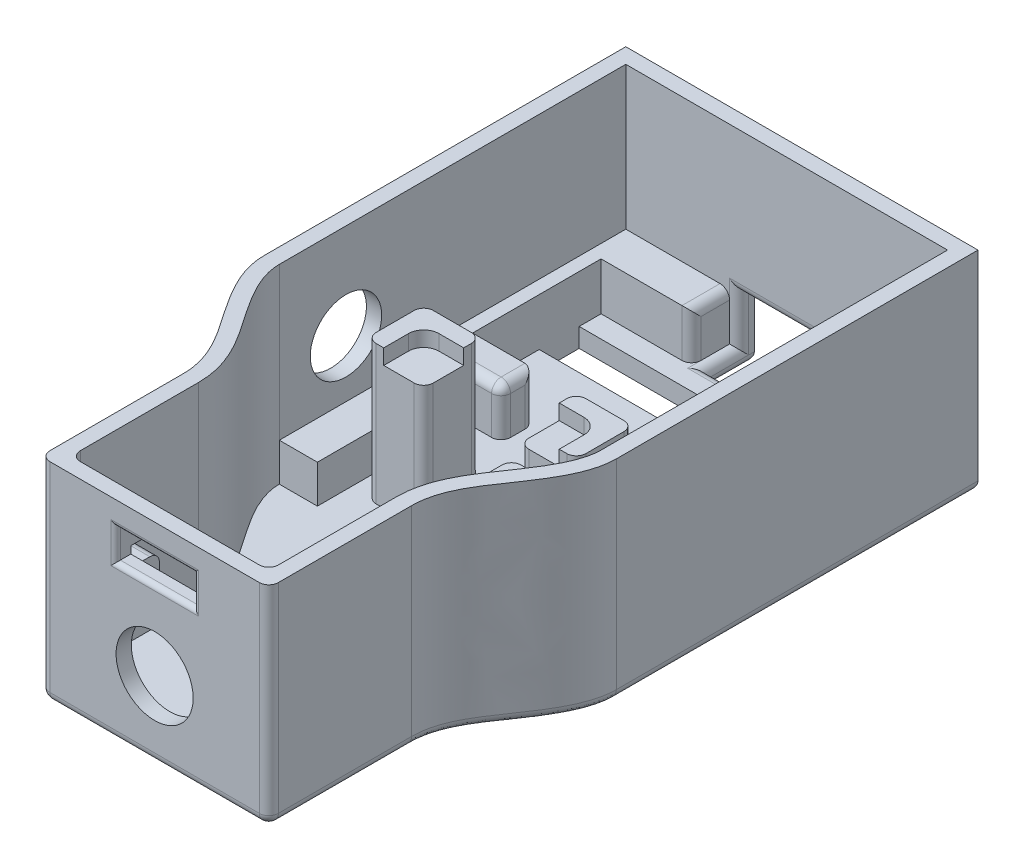
SolidWorks part; units mm, degrees
material "Melamine resin"
ref_plane "Front Plane" through (0, 0, 0) normal (0, 0, 1) x (1, 0, 0)
ref_plane "Top Plane" through (0, 0, 0) normal (0, 1, 0) x (1, 0, 0)
ref_plane "Right Plane" through (0, 0, 0) normal (1, 0, 0) x (0, 0, -1)
sketch "Sketch1" plane through (0, 0, 0) normal (0, 1, 0) x (1, 0, 0)
  line L0 (-18.5, 68) -> (0, 68)
  line L9 (0, 68) -> (0, 0)
  line L10 (-18.5, 68) -> (-18.5, 30)
  line L11 (0, 0) -> (-12, 0)
  line L12 (-12, 0) -> (-12, 15)
  line L13 (-18.5, 30) -> (-12, 30) construction
  line L14 (-12, 30) -> (-12, 15) construction
  line L15 (-15.25, 22.5) -> (-12, 22.5) construction
  line L16 (0, 1.6) -> (-10.4, 1.6)
  line L17 (-15.25, 30) -> (-15.25, 22.5) construction
  line L18 (-10.4, 1.6) -> (-10.4, 15)
  line L19 (-16.9, 66.4) -> (-16.9, 30)
  line L20 (-16.9, 66.4) -> (0, 66.4)
  line L21 (0, 68) -> (0, 66.4)
  line L22 (0, 1.6) -> (0, 0)
  spline S0 degree 3 poles (-18.5, 30) (-18.5, 27.3947) (-15.25, 22.3602) (-12, 17.8849) (-12, 15) knots 0 0 0 0 0.5 1 1 1 1
  spline S1 degree 1 poles (-16.9, 30) (-10.4, 15) knots 0 0 1 1 construction
  spline S2 degree 3 poles (-10.4, 15) (-10.4, 15.4256) (-10.4616, 16.2904) (-10.7983, 17.8861) (-11.54, 19.6983) (-12.6996, 21.6224) (-13.9392, 23.4086) (-15.1181, 25.1604) (-16.1016, 26.879) (-16.6415, 28.2398) (-16.8623, 29.268) (-16.9, 29.7529) (-16.9, 30) knots 0 0 0 0 0.0625 0.125 0.25 0.375 0.5 0.625 0.75 0.875 0.9375 1 1 1 1
  dimension "D1" = 18.5
  dimension "D2" = 68
  dimension "D3" = 15
  dimension "D4" = 15
  dimension "D5" = 12
  dimension "D6" = 1.6
extrude "Boss-Extrude1" add sketch "Sketch1" against normal blind 2 contours S0 L12 L11 L9 L0 L10
extrude "Boss-Extrude2" add sketch "Sketch1<3>" along normal blind 20 contours L18 S2 L19 L20 L9 L0 L10 S0 L12 L11 L16 region at (-9.25, 0, -67.2953)
sketch "Sketch1<3>" plane through (0, 0, 0) normal (0, 1, 0) x (1, 0, 0) same geometry as "Sketch1"
fillet "Fillet1" radius 1 2 edges at (-10.4, 10, -1.6) (-12, 9, 0)
mirror "Mirror1" about plane through (0, 0, 0) normal (1, 0, 0) of "Boss-Extrude2", "Fillet1", "Boss-Extrude1"
sketch "Sketch2" plane through (0, 0, 0) normal (0, 0, 1) x (1, 0, 0)
  line L0 (0, 0) -> (0, 6) construction
  line L1 (0, 6) -> (0, 15.84) construction
  line L2 (4.1, 14.24) -> (-4.1, 14.24)
  line L3 (4.1, 14.24) -> (4.1, 17.44)
  line L4 (4.1, 17.44) -> (-4.1, 17.44)
  line L5 (-4.1, 14.24) -> (-4.1, 17.44)
  line L6 (4.1, 14.24) -> (-4.1, 17.44) construction
  line L7 (4.1, 17.44) -> (-4.1, 14.24) construction
  line L8 (11, 20) -> (-11, 20) construction
  circle A0 centre (0, 6) radius 4.05
  point P4 (0, 15.84)
  dimension "D1" = 8.1
  dimension "D2" = 6
  dimension "D3" = 8.2
  dimension "D4" = 3.2
  dimension "D5" = 4.16
extrude "Cut-Extrude1" cut sketch "Sketch2" against normal up to next
sketch "Sketch3" plane through (0, 0, 0) normal (0, 1, 0) x (1, 0, 0)
  line L0 (-15.5, 55.65) -> (15.5, 55.65) construction
  line L1 (-16.9, 66.4) -> (-6, 66.4)
  line L2 (-16.9, 66.4) -> (-16.9, 45.4)
  line L3 (-16.9, 45.4) -> (-9, 45.4)
  line L4 (16.9, 66.4) -> (16.9, 45.4)
  line L5 (9, 45.4) -> (16.9, 45.4)
  line L7 (-9, 48.9) -> (-9, 45.4)
  line L9 (9, 48.9) -> (9, 45.4)
  line L10 (9, 48.9) -> (15.5, 48.9)
  line L11 (-15.5, 62.4) -> (-6, 62.4)
  line L12 (-15.5, 62.4) -> (-15.5, 48.9)
  line L13 (-15.5, 48.9) -> (-9, 48.9)
  line L14 (15.5, 62.4) -> (15.5, 48.9)
  line L15 (-9, 45.4) -> (9, 45.4) construction
  line L16 (-9, 48.9) -> (9, 48.9) construction
  line L17 (0, 66.4) -> (0, 62.4) construction
  line L18 (0, 62.4) -> (0, 48.9) construction
  line L19 (0, 48.9) -> (0, 45.4) construction
  line L20 (16.9, 66.4) -> (16.9, 30) construction
  line L21 (-6, 62.4) -> (-6, 66.4)
  line L22 (6, 62.4) -> (6, 66.4)
  line L23 (6, 62.4) -> (15.5, 62.4)
  line L24 (6, 66.4) -> (16.9, 66.4)
  line L25 (-6, 66.4) -> (6, 66.4) construction
  line L26 (-16.9, 66.4) -> (16.9, 66.4) construction
  line L27 (-6, 62.4) -> (6, 62.4) construction
  point P23 (0, 55.65)
  dimension "D1" = 31
  dimension "D2" = 13.5
  dimension "D3" = 12
  dimension "D4" = 4
  dimension "D5" = 18
  dimension "D6" = 3.5
extrude "Boss-Extrude3" add sketch "Sketch3" along normal blind 5
ref_plane "IR_mid" through (0, 0, -55.65) normal (0, 0, 1) x (1, 0, 0)
sketch "Sketch4" plane through (0, 0, -68) normal (0, 0, -1) x (-1, 0, 0)
  line L0 (18.5, -2) -> (-18.5, -2) construction
  line L1 (-5, -2) -> (5, -2)
  line L2 (-5, -2) -> (-5, 5)
  line L3 (-5, 5) -> (5, 5)
  line L4 (5, -2) -> (5, 5)
  line L5 (0, 5) -> (0, -2) construction
  dimension "D1" = 10
  dimension "D2" = 7
extrude "Cut-Extrude2" cut sketch "Sketch4" against normal blind 5
sketch "Sketch5" plane through (-18.5, 0, 0) normal (-1, 0, 0) x (0, 0, 1)
  line L0 (-37, 20) -> (-37, 0) construction
  line L1 (-68, 20) -> (-30, 20) construction
  line L2 (-37, 0) -> (0, 0) construction
  circle A0 centre (-37, 10) radius 3.75
  dimension "D1" = 7.5
  dimension "D2" = 37
extrude "Cut-Extrude3" cut sketch "Sketch5" against normal up to next
sketch "Sketch6" plane through (0, 0, 0) normal (0, 1, 0) x (1, 0, 0)
  line L0 (-16.9, 45.4) -> (-16.9, 30) construction
  line L1 (-16.9, 45.4) -> (-12.9, 45.4)
  line L2 (-16.9, 45.4) -> (-16.9, 30)
  line L3 (-16.9, 30) -> (-12.9, 30)
  line L4 (-12.9, 45.4) -> (-12.9, 30)
  spline S0 degree 3 poles (-10.4, 15) (-10.4, 15.4256) (-10.4616, 16.2904) (-10.7983, 17.8861) (-11.54, 19.6983) (-12.6996, 21.6224) (-13.9392, 23.4086) (-15.1181, 25.1604) (-16.1016, 26.879) (-16.6415, 28.2398) (-16.8623, 29.268) (-16.9, 29.7529) (-16.9, 30) knots 0 0 0 0 0.0625 0.125 0.25 0.375 0.5 0.625 0.75 0.875 0.9375 1 1 1 1 construction
  dimension "D1" = 4
extrude "Boss-Extrude4" add sketch "Sketch6" along normal blind 4
sketch "Sketch7" plane through (0, 0, -1.6) normal (0, 0, -1) x (-1, 0, 0)
  line L0 (4.1, 13) -> (9, 13)
  line L1 (11.1, 11) -> (4.1, 11)
  line L4 (4.1, 11) -> (4.1, 13)
  line L5 (9, 13) -> (9, 15)
  line L10 (4.1, 11) -> (0, 11) construction
  line L11 (9, 15) -> (4.1, 15)
  line L12 (-9.4, 0) -> (9.4, 0) construction
  line L13 (0, 0) -> (0, 11) construction
  line L14 (4.1, 15) -> (4.1, 17)
  line L15 (4.1, 17) -> (11.1, 17)
  line L16 (11.1, 11) -> (11.1, 17)
  line L17 (4.1, 13) -> (4.1, 15) construction
  dimension "D1" = 7
  dimension "D2" = 2
  dimension "D3" = 11
  dimension "D4" = 4.1
  dimension "D5" = 2
  dimension "D6" = 9
extrude "Boss-Extrude5" add sketch "Sketch7" along normal blind 3
sketch "Sketch9" plane through (0, 0, 0) normal (0, 1, 0) x (1, 0, 0)
  line L0 (0, 0) -> (0, 36.788) construction
  line L1 (-5.018, 33.288) -> (-11.018, 33.288)
  line L2 (-5.018, 33.288) -> (-5.018, 39.288)
  line L3 (-5.018, 39.288) -> (-11.018, 39.288)
  line L4 (-11.018, 33.288) -> (-11.018, 39.288)
  line L5 (-8.518, 36.788) -> (-8.518, 39.288) construction
  line L6 (-8.518, 36.788) -> (-11.018, 36.788) construction
  line L7 (0, 36.788) -> (-8.518, 36.788) construction
  point P0 (-8.518, 36.788)
  dimension "D1" = 2.5
  dimension "D2" = 2.5
  dimension "D3" = 8.518
  dimension "D4" = 36.788
  dimension "D5" = 6
  dimension "D6" = 6
extrude "Boss-Extrude7" add sketch "Sketch9" along normal up to surface (13 mm away) up to face at (-6.55, 13, -3.1)
sketch "Sketch10" plane through (0, 13, 0) normal (0, 1, 0) x (1, 0, 0)
  line L0 (-11.018, 39.288) -> (-11.018, 33.288)
  line L1 (-11.018, 33.288) -> (-11.018, 39.288) construction
  line L2 (-5.018, 33.288) -> (-11.018, 33.288) construction
  line L3 (-11.018, 33.288) -> (-9.218, 33.288)
  line L4 (-9.218, 33.288) -> (-9.218, 37.488) construction
  line L5 (-9.218, 37.488) -> (-5.018, 37.488) construction
  line L6 (-5.018, 39.288) -> (-5.018, 33.288) construction
  line L7 (-5.018, 37.488) -> (-5.018, 39.288)
  line L8 (-5.018, 39.288) -> (-11.018, 39.288)
  line L10 (-11.018, 39.288) -> (-5.018, 39.288) construction
  line L11 (-5.018, 37.488) -> (-7.618, 37.488)
  line L12 (-9.218, 33.288) -> (-9.218, 35.888)
  arc A0 (-9.218, 35.888) -> (-7.618, 37.488) centre (-7.618, 35.888) cw
  dimension "D2" = 1.6
  dimension "D1" = 1.8
extrude "Boss-Extrude8" add sketch "Sketch10" along normal blind 1.6
mirror "Mirror2" about plane through (0, 0, 0) normal (1, 0, 0) of "Boss-Extrude8", "Boss-Extrude5", "Boss-Extrude7"
sketch "Sketch11" plane through (0, 0, 0) normal (0, 1, 0) x (1, 0, 0)
  line L1 (5, 42.488) -> (-5, 42.488)
  line L2 (5, 42.488) -> (5, 37.488)
  line L3 (5, 37.488) -> (-5, 37.488)
  line L4 (-5, 42.488) -> (-5, 37.488)
  line L5 (5, 42.488) -> (-5, 37.488) construction
  line L6 (5, 37.488) -> (-5, 42.488) construction
  circle A0 centre (0, 39.988) radius 1.25 construction
  point P0 (0, 39.988)
  dimension "D1" = 10
  dimension "D2" = 5
extrude "Boss-Extrude9" add sketch "Sketch11" along normal blind 1.95
fillet "Fillet2" radius 1 28 edges at (-6, 2.5, -62.4) (-9, 2.5, -48.9) (-11.018, 7.3, -33.288) (-11.018, 7.3, -39.288) (-5, 0.975, -42.488) (-9, 2.5, -45.4) (0, 5, -66.4) (5, 2.5, -66.4) (-5, 2.5, -66.4) (-5, 0, -64.7) (5, 0, -64.7) (0, 0, -63) (6, 2.5, -62.4) (9, 2.5, -45.4) (9, 2.5, -48.9) (11.018, 7.3, -33.288) (11.018, 7.3, -39.288) (5, 0.975, -42.488) (5.018, 6.5, -33.288) (-5.018, 6.5, -33.288) (5.018, 7.3, -39.288) (-5.018, 7.3, -39.288) (6, 5, -64.4) (-6, 5, -64.4) (-9, 5, -47.15) (9, 5, -47.15) (-12.95, 5, -45.4) (12.95, 5, -45.4)
sketch "Sketch12" plane through (0, 1.95, 0) normal (0, 1, 0) x (1, 0, 0)
  circle A0 centre (0, 39.988) radius 1.7
  dimension "D1" = 3.4
extrude "Cut-Extrude4" cut sketch "Sketch12" against normal up to next
chamfer "Chamfer1" distance 1.8 angle 45 1 edges at (0, -2, -41.688)
fillet "Fillet3" radius 0.5 1 edges at (0, -0.2, -41.688)
chamfer "Chamfer2" distance 1.95 angle 45 6 edges at (0, 0, -37.488) (-5, 0, -39.488) (-4.7071, 0, -42.1951) (5, 0, -39.488) (4.7071, 0, -42.1951) (0, 0, -42.488)
fillet "Fillet4" radius 0.5 4 edges at (4.1, 15.84, 0) (0, 14.24, 0) (0, 17.44, 0) (-4.1, 15.84, 0)
fillet "Fillet5" radius 1 6 edges at (9, 14, -4.6) (6.55, 13, -4.6) (6.55, 15, -4.6) (-6.55, 13, -4.6) (-9, 14, -4.6) (-6.55, 15, -4.6)
sketch "Sketch13" plane through (0, 0, 0) normal (1, 0, 0) x (0, 0, -1)
  line L0 (68, -2) -> (30, -2) construction
  line L1 (55.9, -2) -> (60.1, -2)
  line L2 (55.9, -2) -> (55.9, 0)
  line L3 (55.9, 0) -> (60.1, 0)
  line L4 (60.1, -2) -> (60.1, 0)
  line L5 (48.9, 0) -> (62.4, 0) construction
  line L6 (68, -2) -> (68, 5) construction
  point P8 (58, -2)
  dimension "D1" = 10
  dimension "D2" = 4.2
extrude "Cut-Extrude5" cut sketch "Sketch13" against normal up to surface and the other way up to surface up to face at (-15.5, 2.5, -55.65) other way up to face at (15.5, 2.5, -55.65)
ref_plane "suspension_plate" through (0, 0, -58) normal (0, 0, -1) x (-1, 0, 0)
fillet "Fillet6" radius 1 14 edges at (-18.5, -2, -49) (-12, -2, -8) (-11.7071, -2, -0.2929) (0, -2, 0) (11.7071, -2, -0.2929) (18.5, -2, -49) (5, -2, -65.5) (0, -2, -63) (-5, -2, -65.5) (-11.75, -2, -68) (11.75, -2, -68) (12, -2, -8)
